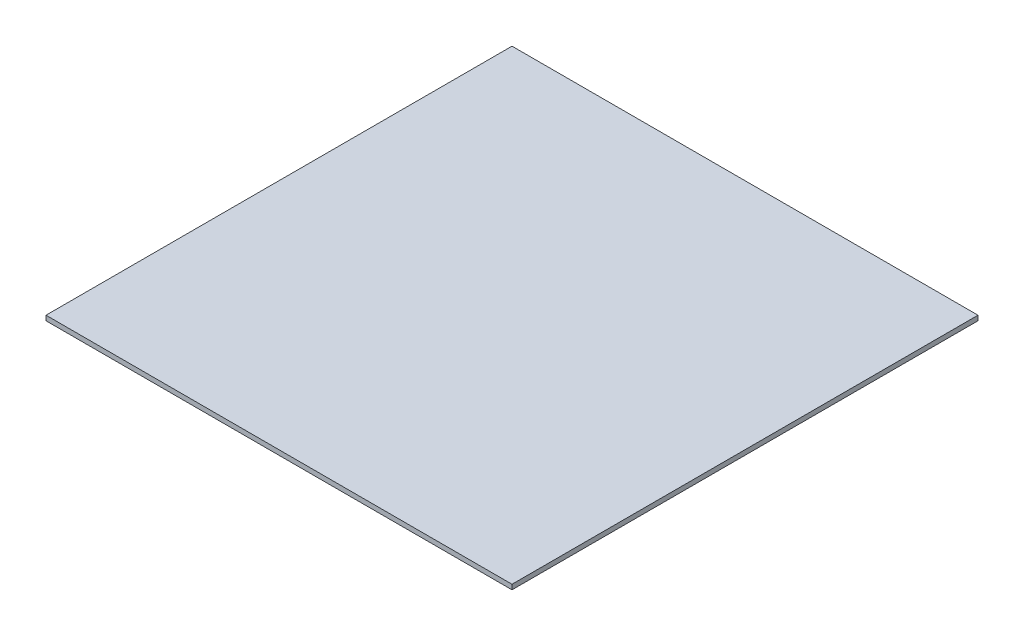
SolidWorks part; units mm, degrees
material "Acrylic (Medium-high impact)"
ref_plane "Front Plane" through (0, 0, 0) normal (0, 0, 1) x (1, 0, 0)
ref_plane "Top Plane" through (0, 0, 0) normal (0, 1, 0) x (1, 0, 0)
ref_plane "Right Plane" through (0, 0, 0) normal (1, 0, 0) x (0, 0, -1)
sketch "Sketch1" plane through (0, 0, 0) normal (0, 1, 0) x (1, 0, 0)
  line L1 (-304.8, -304.8) -> (304.8, -304.8)
  line L2 (-304.8, -304.8) -> (-304.8, 304.8)
  line L3 (-304.8, 304.8) -> (304.8, 304.8)
  line L4 (304.8, -304.8) -> (304.8, 304.8)
  line L5 (-304.8, -304.8) -> (304.8, 304.8) construction
  line L6 (-304.8, 304.8) -> (304.8, -304.8) construction
  point P0 (0, 0)
  dimension "D1" = 609.6
  dimension "D2" = 609.6
extrude "Boss-Extrude1" add sketch "Sketch1" along normal mid plane 6.35
sketch "Sketch2" plane through (0, 3.175, 0) normal (0, 1, 0) x (1, 0, 0)
  line L0 (-304.8, -304.8) -> (-304.8, 304.8)
  line L1 (-304.8, 304.8) -> (304.8, 304.8)
  line L2 (304.8, 304.8) -> (-304.8, 304.8) construction
  line L3 (304.8, 304.8) -> (304.8, 152.4)
  line L4 (304.8, -304.8) -> (304.8, 304.8) construction
  line L5 (304.8, 152.4) -> (-152.4, 152.4)
  line L6 (-152.4, 152.4) -> (-152.4, -304.8)
  line L7 (-304.8, -304.8) -> (304.8, -304.8) construction
  line L8 (-152.4, -304.8) -> (-304.8, -304.8)
  dimension "D1" = 152.4
  dimension "D2" = 152.4
  dimension "D3" = 90
extrude "Cut-Extrude1" [suppressed] cut sketch "Sketch2" against normal through all both and the other way through all
